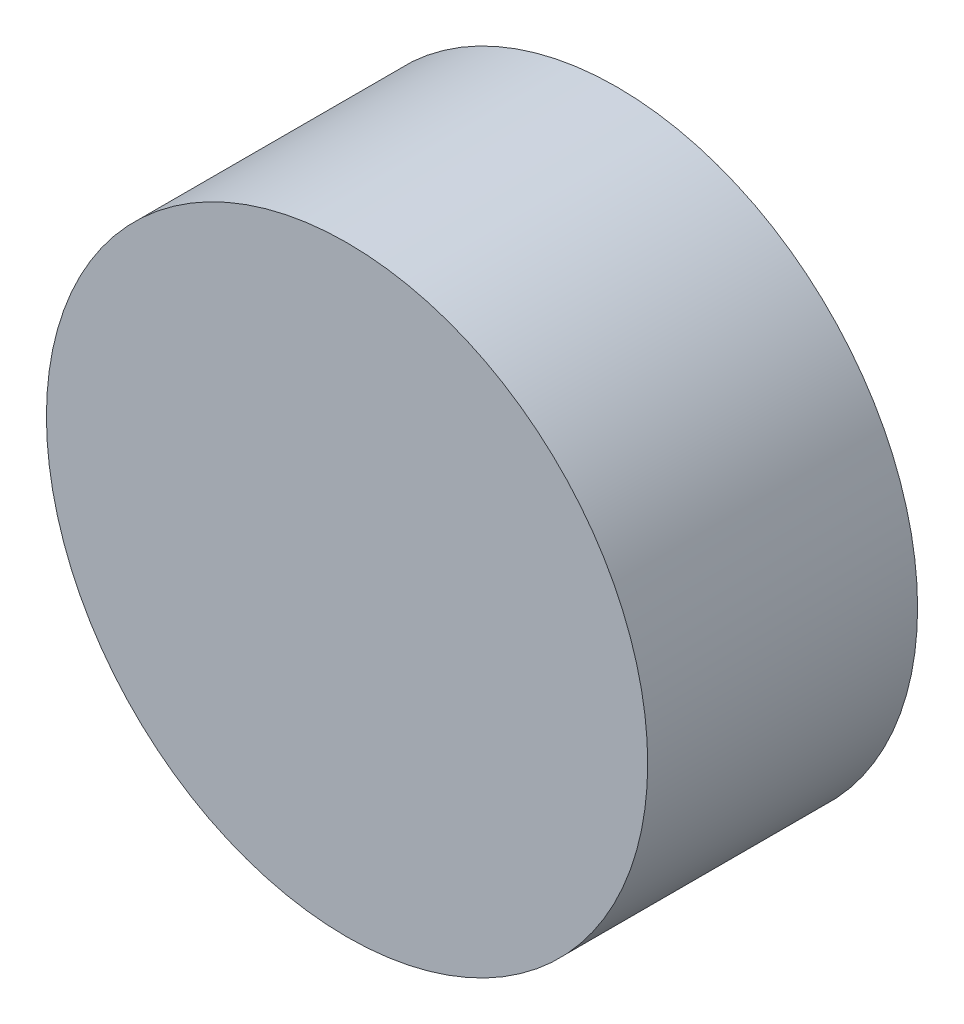
SolidWorks part; units mm, degrees
material "Filter_Bulk_6061Properties"
ref_plane "Front Plane" through (0, 0, 0) normal (0, 0, 1) x (1, 0, 0)
ref_plane "Top Plane" through (0, 0, 0) normal (0, 1, 0) x (1, 0, 0)
ref_plane "Right Plane" through (0, 0, 0) normal (1, 0, 0) x (0, 0, -1)
sketch "Sketch1" plane through (0, 0, 0) normal (0, 0, 1) x (1, 0, 0)
  circle A0 centre (0, 0) radius 12.7
  circle A1 centre (0, 0) radius 12.7 construction
extrude "Boss-Extrude1" add sketch "Sketch1" along normal blind 11.4
